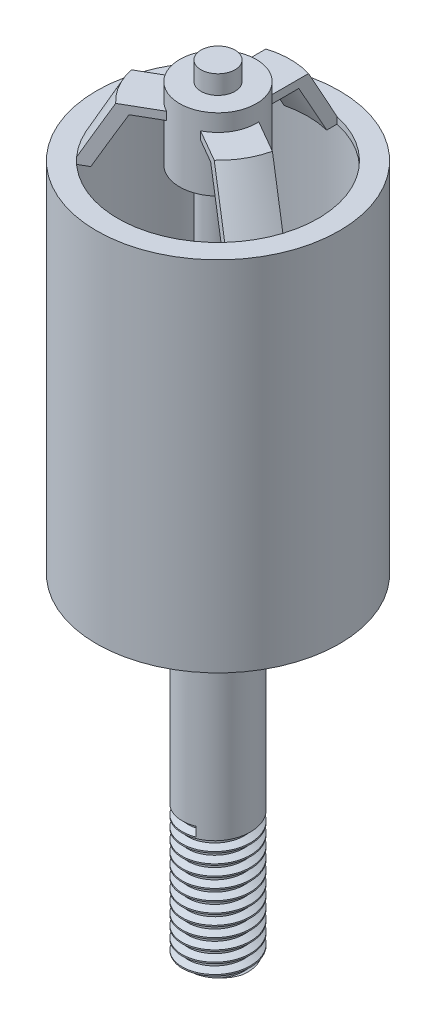
SolidWorks part; units mm, degrees
material "1.5714 (16NiCr4)"
ref_plane "Спереди" through (0, 0, 0) normal (0, 0, 1) x (1, 0, 0)
ref_plane "Сверху" through (0, 0, 0) normal (0, 1, 0) x (1, 0, 0)
ref_plane "Справа" through (0, 0, 0) normal (1, 0, 0) x (0, 0, -1)
sketch "Эскиз1" plane through (0, 0, 0) normal (0, 0, 1) x (1, 0, 0)
  line L2 (2, 88.8) -> (4.5, 88.8)
  line L3 (4.5, 88.8) -> (4.5, 86.8)
  line L4 (4.5, 86.8) -> (8.5, 86.8)
  line L5 (8.5, 86.8) -> (11.75, 80.7437)
  line L6 (11.75, 80.7437) -> (14.25, 80.7437)
  line L7 (14.25, 80.7437) -> (14.25, 38.7437)
  line L13 (13.2587, 38.7437) -> (13.2587, 79.981)
  line L14 (13.2587, 79.981) -> (10.5648, 79.981)
  line L15 (10.5648, 79.981) -> (7.4123, 85.8556)
  line L18 (0, 0) -> (0, 91) construction
  line L19 (4.5, 85.8556) -> (4.5, 80.327)
  line L20 (4.5, 80.327) -> (2, 80.327)
  line L21 (4.5, 85.8556) -> (7.4123, 85.8556)
  line L24 (13.2587, 38.7437) -> (14.25, 38.7437)
  line L25 (2, 88.8) -> (2, 80.327)
  dimension "D1" = 91
  dimension "D2" = 42
  dimension "D5" = 14.25
  dimension "D7" = 2
revolve "Повернуть1" add sketch "Эскиз1" angle 360 about L18
sketch "Эскиз2" plane through (0, 86.8, 0) normal (0, 1, 0) x (1, 0, 0)
  line L4 (11.3063, -9.4145) -> (-1.25, -2.1651) construction
  line L5 (-2.5, 0) -> (-2.5, 14.4988) construction
  line L6 (1.25, 2.1651) -> (13.8063, -5.0843) construction
  line L7 (2.5, 14.4988) -> (2.5, 0) construction
  line L8 (-13.8063, -5.0843) -> (-1.25, 2.1651) construction
  line L9 (1.25, -2.1651) -> (-11.3063, -9.4145) construction
  line L16 (-2.5, 3.7417) -> (-2.5, 11.481)
  line L17 (-4.4904, 0.2942) -> (-11.1928, -3.5754)
  line L18 (-8.6928, -7.9055) -> (-1.9904, -4.0359)
  line L19 (1.9904, -4.0359) -> (8.6928, -7.9055)
  line L20 (4.4904, 0.2942) -> (11.1928, -3.5754)
  line L21 (2.5, 3.7417) -> (2.5, 11.481)
  circle A12 centre (0, 0) radius 4.5 construction
  circle A13 centre (0, 0) radius 11.75 construction
  arc A14 (-2.5, 11.481) -> (-11.1928, -3.5754) centre (0, 0) ccw
  arc A15 (2.5, 11.481) -> (11.1928, -3.5754) centre (0, 0) cw
  arc A16 (8.6928, -7.9055) -> (-8.6928, -7.9055) centre (0, 0) cw
  arc A17 (-2.5, 3.7417) -> (-4.4904, 0.2942) centre (0, 0) ccw
  arc A18 (-1.9904, -4.0359) -> (1.9904, -4.0359) centre (0, 0) ccw
  arc A19 (4.4904, 0.2942) -> (2.5, 3.7417) centre (0, 0) ccw
  point P19 (0, 0)
  dimension "D1" = 3
extrude "Вырез-Вытянуть1" cut sketch "Эскиз2" against normal blind 10
sketch "Эскиз20" plane through (0, 88.8, 0) normal (0, 1, 0) x (1, 0, 0)
  circle A0 centre (0, 0) radius 2
extrude "Бобышка-Вытянуть2" add sketch "Эскиз20" along normal blind 2.2 and the other way blind 50
sketch "Эскиз21" plane through (0, 38.8, 0) normal (0, -1, 0) x (1, 0, 0)
  circle A0 centre (0, 0) radius 4
extrude "Бобышка-Вытянуть3" add sketch "Эскиз21" along normal up to vertex (38.8 mm away) up to point (0, 0, 0)
chamfer "Фаска1" distance 0.5 angle 45 1 edges at (4, 0, 0)
thread "Резьба3" pitch 1.25 method cut profile "Профиль резьбы3" start angle 0, offset 2, length 16, pitch 1.25, diameter 8
ref_plane "Плоскость3" through (4, -1.5, 0) normal (0, 0, 1) x (1, 0, 0)
sketch "Профиль резьбы3" plane through (4, -1.5, 0) normal (0, 0, 1) x (1, 0, 0)
  line L0 (0, 0) -> (0, 1.25) construction
  line L11 (0, 0) -> (0, 1.0937)
  line L12 (0, 1.0937) -> (-0.6766, 0.7031)
  line L13 (-0.6766, 0.7031) -> (-0.6766, 0.3906)
  line L15 (-0.6766, 0.3906) -> (0, 0)
  line L17 (-0.6766, 0.5469) -> (0, 0.5469) construction
  point P2 (0, 0)
  dimension "Pitch" = 1.25
  dimension "Profile_Angle" = 60
  dimension "Profile_Land" = 0.3125
  dimension "Profile_Height" = 0.6766
